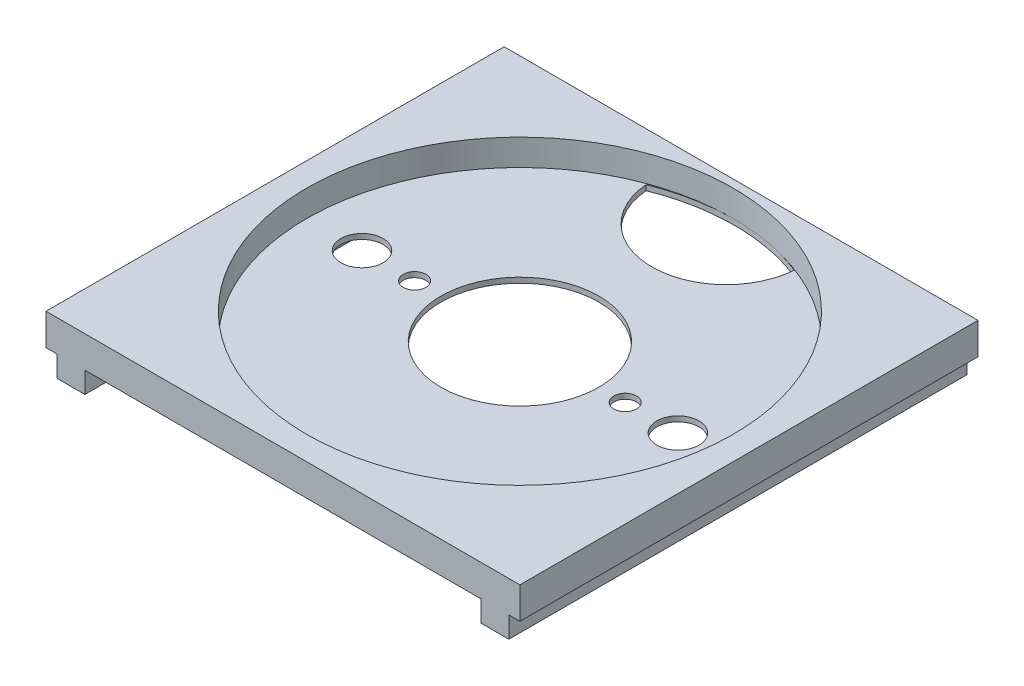
SolidWorks part; units mm, degrees
ref_plane "Front Plane" through (0, 0, 0) normal (0, 0, 1) x (1, 0, 0)
ref_plane "Top Plane" through (0, 0, 0) normal (0, 1, 0) x (1, 0, 0)
ref_plane "Right Plane" through (0, 0, 0) normal (1, 0, 0) x (0, 0, -1)
sketch "Sketch1" plane through (0, 0, 0) normal (0, 1, 0) x (1, 0, 0)
  line L2 (0, -45) -> (-45, -45)
  line L3 (-45, -45) -> (-45, 45)
  line L4 (-45, 45) -> (0, 45)
  line L5 (0, 45) -> (45, 45)
  line L6 (45, 45) -> (45, -45)
  line L7 (45, -45) -> (0, -45)
extrude "Boss-Extrude1" add sketch "Sketch1" along normal blind 10
sketch "Sketch2" plane through (0, 10, 0) normal (0, 1, 0) x (1, 0, 0)
  circle A0 centre (0, 0) radius 40.5
extrude "Cut-Extrude1" cut sketch "Sketch2" against normal blind 5 contours A0
sketch "Sketch4" plane through (0, 5, 0) normal (0, 1, 0) x (1, 0, 0)
  circle A2 centre (-20, 0) radius 2.15
  circle A3 centre (20, 0) radius 2.15
extrude "Cut-Extrude2" cut sketch "Sketch4" against normal blind 2
sketch "Sketch5" plane through (0, 5, 0) normal (0, 1, 0) x (1, 0, 0)
  circle A0 centre (0, 0) radius 15
extrude "Cut-Extrude3" cut sketch "Sketch5" against normal through all
sketch "Sketch7" plane through (0, 5, 0) normal (0, 1, 0) x (1, 0, 0)
  arc A0 (-13.8415, 37.8005) -> (14.3106, 37.8005) centre (0.2345, 38.9392) ccw
  arc A1 (-13.8415, 37.8005) -> (14.3106, 37.8005) centre (0.2345, 2.5037) cw
extrude "Cut-Extrude4" cut sketch "Sketch7" against normal blind 66 contours A0 A1
sketch "Sketch8" plane through (0, 0, 0) normal (0, -1, 0) x (1, 0, 0)
  line L0 (-45, 45) -> (45, 45)
  line L1 (45, 45) -> (45, -45)
  line L2 (45, -45) -> (-45, -45)
  line L3 (-45, -45) -> (-45, 45)
extrude "Boss-Extrude2" add sketch "Sketch8" along normal blind 45
sketch "Sketch9" plane through (0, 0, 45) normal (0, 0, 1) x (1, 0, 0)
  line L0 (-45, -45) -> (-35, -45)
  line L1 (45, -45) -> (-45, -45) construction
  line L2 (-35, -45) -> (-35, 4)
  line L3 (-35, 4) -> (35, 4)
  line L4 (35, 4) -> (35, -45)
  line L5 (35, -45) -> (-35, -45)
extrude "Cut-Extrude5" cut sketch "Sketch9" against normal blind 68 contours L2 L3 L4 L5
sketch "Sketch10" plane through (0, 0, -45) normal (0, 0, -1) x (-1, 0, 0)
  line L8 (0, 10) -> (0, -45) construction
  line L9 (-45, 10) -> (45, 10) construction
  line L13 (45, -45) -> (-45, -45) construction
  line L14 (-45, -17.5) -> (45, -17.5) construction
  line L15 (-45, 10) -> (-45, -45) construction
  line L16 (45, 10) -> (45, -45) construction
  line L29 (-12, -21) -> (-12, -25)
  line L36 (-12, -25) -> (-18, -25)
  line L37 (-12, -21) -> (-12, -2)
  line L39 (-12, -2) -> (-12, 1)
  line L40 (-12, 1) -> (12, 1)
  line L41 (12, -25) -> (12, 1)
  line L42 (12, -25) -> (18.3379, -25)
  line L43 (-18, -25) -> (-18, -37)
  line L44 (18.3379, -25) -> (18.3379, -37)
  line L45 (18.3379, -37) -> (-18, -37)
extrude "Cut-Extrude7" cut sketch "Sketch10" against normal blind 20
sketch "Sketch12" plane through (0, 0, -45) normal (0, 0, -1) x (-1, 0, 0)
  text T0 "ProtoPill\r\nDispenser\r\nTesterV5\r\n"
extrude "Cut-Extrude9" cut sketch "Sketch12" against normal blind 4
sketch "Sketch17" plane through (0, -37, 0) normal (0, 1, 0) x (1, 0, 0)
  line L0 (-0.1689, 24) -> (-0.1689, 45) construction
  line L2 (18, 45) -> (-18.3379, 45) construction
  line L3 (18, 35) -> (-18.3379, 35) construction
  line L4 (18, 25) -> (18, 45) construction
  line L5 (-18.3379, 25) -> (-18.3379, 45) construction
  line L6 (11.8311, 35) -> (11.8311, 26.5)
  line L7 (-12.1689, 35) -> (-12.1689, 42.5)
  line L8 (-12.1689, 35) -> (-12.1689, 26.5)
  line L9 (11.8311, 35) -> (11.8311, 42.5)
  line L10 (11.8311, 26.5) -> (-12.1689, 26.5)
  line L11 (-12.1689, 42.5) -> (11.8311, 42.5)
extrude "Cut-Extrude12" cut sketch "Sketch17" against normal blind 3
sketch "Sketch18" plane through (0, -40, 0) normal (0, 1, 0) x (1, 0, 0)
  circle A0 centre (-0.1689, 32.5) radius 11.15
  dimension "D1" = 22.3
extrude "Cut-Extrude13" cut sketch "Sketch18" against normal blind 4.66
sketch "Sketch20" plane through (-12, 0, 0) normal (1, 0, 0) x (0, 0, -1)
  line L0 (35, -25) -> (35, 0) construction
  line L1 (25, -25) -> (45, -25) construction
  line L2 (38.4803, 0) -> (31.8859, 0) construction
  line L10 (28.17, -1.7) -> (41.83, -1.7)
  line L13 (41.83, -1.7) -> (41.83, -26.5)
  line L14 (28.17, -26.5) -> (41.83, -26.5)
  line L15 (28.17, -26.5) -> (28.17, -1.7)
extrude "Cut-Extrude14" cut sketch "Sketch20" against normal blind 14.5
sketch "Sketch22" plane through (-26.5, 0, 0) normal (1, 0, 0) x (0, 0, -1)
  line L0 (35, -26.5) -> (35, -1.7) construction
  line L3 (28.17, -17.05) -> (41.83, -17.05) construction
  line L6 (28.17, -26.5) -> (41.83, -26.5) construction
  line L7 (41.83, -1.7) -> (28.17, -1.7) construction
  line L8 (28.17, -1.7) -> (28.17, -26.5) construction
  line L9 (41.83, -26.5) -> (41.83, -1.7) construction
  circle A0 centre (35, -17.05) radius 1.45
  dimension "D1" = 2.9
extrude "Boss-Extrude3" add sketch "Sketch22" along normal blind 9
sketch "Sketch24" plane through (12, 0, 0) normal (-1, 0, 0) x (0, 0, 1)
  line L0 (-41.83, -1.7) -> (-28.17, -1.7) construction
  line L1 (-28.17, -1.7) -> (-28.17, -26.5)
  line L4 (-41.83, -1.7) -> (-28.17, -1.7)
  line L13 (-41.83, -1.7) -> (-41.83, -26.5)
  line L14 (-41.83, -26.5) -> (-28.17, -26.5)
  circle A0 centre (-35, -17.05) radius 1.45 construction
  circle A1 centre (-35, -17.05) radius 1.45
  dimension "D2" = 2.9
  dimension "D1" = 13.66
extrude "Cut-Extrude16" cut sketch "Sketch24" against normal blind 14.5
sketch "Sketch40" plane through (0, 0, -28.17) normal (0, 0, -1) x (-1, 0, 0)
  line L0 (-26.5, -26.5) -> (-18, -26.5)
  line L3 (-12, -25) -> (-12, -17.0937)
  line L4 (-12, -25) -> (-12, -1.7) construction
  line L5 (-12, -17.0937) -> (-26.5, -17.0937)
  line L6 (-26.5, -26.5) -> (-26.5, -1.7) construction
  line L7 (-26.5, -17.0937) -> (-26.5, -26.5)
  line L8 (0, 0) -> (0, -35.411) construction
  line L9 (26.5, -17.0937) -> (26.5, -26.5)
  line L10 (12, -17.0937) -> (26.5, -17.0937)
  line L11 (12, -25) -> (12, -17.0937)
  line L14 (26.5, -26.5) -> (18, -26.5)
  line L15 (-12, -25) -> (-12, -26.5)
  line L16 (-12, -26.5) -> (-18, -26.5)
  line L17 (12, -25) -> (12, -26.5)
  line L18 (12, -26.5) -> (18, -26.5)
extrude "Cut-Extrude29" cut sketch "Sketch40" against normal blind 10
sketch "Sketch32" plane through (0, 0, -23) normal (0, 0, 1) x (1, 0, 0)
  line L0 (-6.0061, -40) -> (-6.0061, -44.66)
  line L9 (-0.1689, -40) -> (-0.1689, -44.66) construction
  line L10 (-5.1007, -40) -> (4.7628, -40) construction
  line L11 (10.9811, -44.66) -> (-11.3189, -44.66) construction
  line L25 (10.9711, -40) -> (5.6682, -40)
  line L26 (-11.3089, -40) -> (-11.3089, -44.66)
  line L27 (-11.3089, -44.66) -> (-6.0061, -44.66)
  line L28 (-11.3089, -40) -> (-6.0061, -40)
  line L29 (10.9711, -44.66) -> (5.6682, -44.66)
  line L30 (10.9711, -40) -> (10.9711, -44.66)
  line L31 (5.6682, -40) -> (5.6682, -44.66)
extrude "Cut-Extrude21" cut sketch "Sketch32" against normal blind 10
sketch "Sketch33" plane through (0, 5, 0) normal (0, 1, 0) x (1, 0, 0)
  circle A0 centre (-29.9677, -0.0225) radius 4
  circle A1 centre (30.0323, -0.0225) radius 4
extrude "Cut-Extrude22" cut sketch "Sketch33" against normal blind 10
sketch "Sketch41" plane through (0, 4, 0) normal (0, -1, 0) x (1, 0, 0)
sketch "Sketch42" plane through (-35, 0, 0) normal (1, 0, 0) x (0, 0, -1)
  line L0 (0, 4) -> (0, 3.7549) construction
  line L1 (23, 4) -> (-45, 4) construction
  line L2 (0, 3.7549) -> (-6.5633, 3.7549)
  line L3 (0, 3.7549) -> (6.4367, 3.7549)
  line L4 (6.4367, 3.7549) -> (6.4367, -0.2451)
  line L5 (6.4367, -0.2451) -> (-6.5633, -0.2451)
  line L6 (-6.5633, -0.2451) -> (-6.5633, 3.7549)
extrude "Boss-Extrude5" add sketch "Sketch42" along normal blind 10.61
sketch "Sketch45" plane through (35, 0, 0) normal (-1, 0, 0) x (0, 0, 1)
  line L12 (6.5633, 3.7549) -> (-6.4367, 3.7549)
  line L13 (6.5633, -0.2451) -> (6.5633, 3.7549)
  line L14 (-6.4367, -0.2451) -> (6.5633, -0.2451)
  line L15 (-6.4367, 3.7549) -> (-6.4367, -0.2451)
  line L16 (6.5633, 3.7549) -> (-6.4367, 3.7549)
  line L17 (6.5633, -0.2451) -> (6.5633, 3.7549)
  line L18 (-6.4367, -0.2451) -> (6.5633, -0.2451)
  line L19 (-6.4367, 3.7549) -> (-6.4367, -0.2451)
  dimension "D2" = 0
extrude "Boss-Extrude6" add sketch "Sketch45" along normal blind 10.61
sketch "Sketch46" plane through (0, 0, 45) normal (0, 0, 1) x (1, 0, 0)
  line L0 (-43, 4) -> (-45, 4)
  line L1 (-45, 4) -> (-45, -45)
  line L2 (-45, -45) -> (45, -45)
  line L3 (-45, 10) -> (-45, -45) construction
  line L4 (-43, 4) -> (-43, 0)
  line L5 (-43, 0) -> (-37.5166, 0)
  line L6 (45, -45) -> (45, 4)
  line L7 (43, 4) -> (45, 4)
  line L8 (-37.5166, 0) -> (-37.5166, 4)
  line L9 (-37.5166, 4) -> (37.5166, 4)
  line L10 (-35, 4) -> (35, 4) construction
  line L11 (43, 0) -> (43, 4)
  line L14 (-45, 10) -> (45, 10) construction
  line L15 (0, 10) -> (0, 4)
  line L16 (0, 4) -> (2.961, 4)
  line L18 (43, 4) -> (45, 4)
  line L19 (43, 4) -> (43, 0)
  line L20 (43, 0) -> (37.5166, 0)
  line L21 (37.5166, 0) -> (37.5166, 4)
extrude "Cut-Extrude31" cut sketch "Sketch46" against normal blind 87 contours L18 L19 L20 L21 L9 L8 L5 L4 L0 L1 L2 L6
sketch "Sketch49" plane through (0, 0, -42) normal (0, 0, 1) x (1, 0, 0)
  line L0 (-45, 0) -> (45, 0)
  line L1 (-45, 4) -> (-45, -45) construction
  line L2 (45, -45) -> (45, 4) construction
  line L3 (45, 0) -> (45, -45)
  line L4 (45, -45) -> (-45, -45)
  line L5 (-45, -45) -> (45, -45) construction
  line L6 (-45, -45) -> (-45, 0)
extrude "Cut-Extrude32" cut sketch "Sketch49" against normal through all
sketch "Sketch50" plane through (-45, 0, 0) normal (-1, 0, 0) x (0, 0, 1)
  line L0 (-45, 0) -> (-42, 0)
  line L1 (-42, 0) -> (-42, 10)
  line L2 (-45, 10) -> (45, 10) construction
  line L3 (-42, 10) -> (-45, 10)
  line L4 (-45, 10) -> (-45, 0)
extrude "Cut-Extrude33" cut sketch "Sketch50" against normal through all
sketch "Sketch51" plane through (0, 0, 45) normal (0, 0, 1) x (1, 0, 0)
  line L0 (-37.6166, 4) -> (-37.6166, 0)
  line L1 (-43, 4) -> (-42.9, 4)
  line L2 (-42.9, 4) -> (-42.9, 0)
  line L3 (-43, 0) -> (-37.5166, 0) construction
  line L4 (-37.5166, 4) -> (-37.6166, 4)
  line L5 (-37.6166, 0) -> (-37.5166, 0)
  line L6 (-37.5166, 0) -> (-37.5166, 4)
  line L7 (-43, 4) -> (-43, 0)
  line L8 (-43, 0) -> (-42.9, 0)
  line L9 (0, 10) -> (0, 4) construction
  line L10 (-45, 10) -> (45, 10) construction
  line L11 (-37.5166, 4) -> (37.5166, 4) construction
  line L12 (37.6166, 0) -> (37.5166, 0)
  line L13 (37.6166, 4) -> (37.6166, 0)
  line L14 (37.5166, 4) -> (37.6166, 4)
  line L15 (37.5166, 0) -> (37.5166, 4)
  line L16 (43, 4) -> (43, 0)
  line L17 (43, 4) -> (42.9, 4)
  line L18 (42.9, 4) -> (42.9, 0)
  line L19 (43, 0) -> (42.9, 0)
  point P28 (0, 0)
extrude "Cut-Extrude34" cut sketch "Sketch51" against normal through all both and the other way through all
